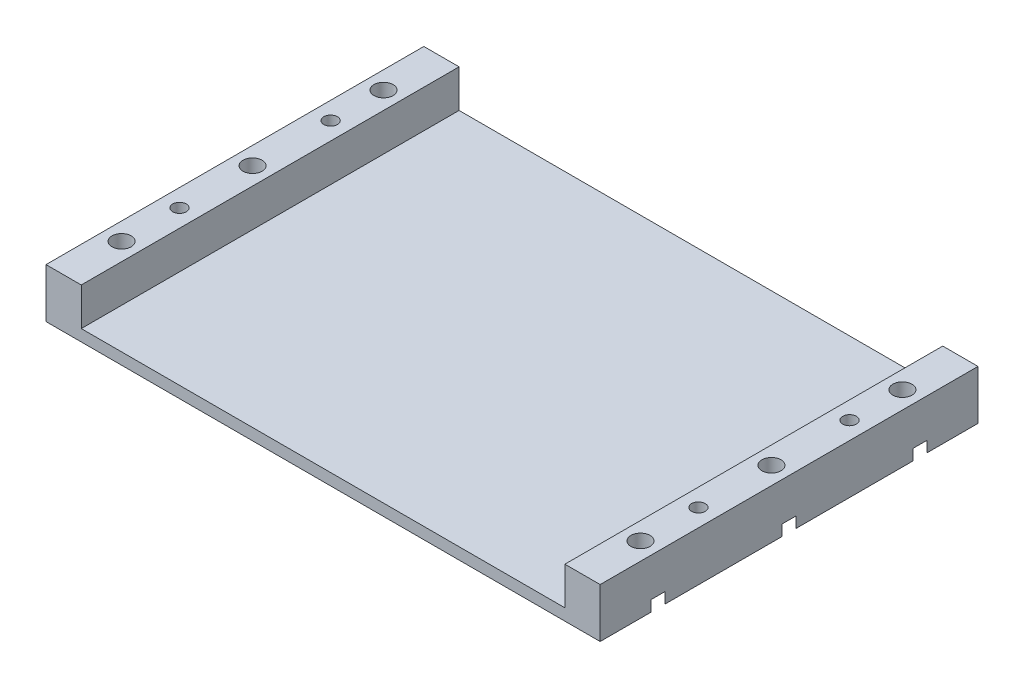
SolidWorks part; units mm, degrees
ref_plane "Front Plane" through (0, 0, 0) normal (0, 0, 1) x (1, 0, 0)
ref_plane "Top Plane" through (0, 0, 0) normal (0, 1, 0) x (1, 0, 0)
ref_plane "Right Plane" through (0, 0, 0) normal (1, 0, 0) x (0, 0, -1)
sketch "Sketch1" plane through (0, 0, 0) normal (0, 1, 0) x (1, 0, 0)
  line L0 (0, 73.5868) -> (1.4132, 75) construction
  line L1 (0, 0) -> (96, 0)
  line L2 (0, 0) -> (0, 75)
  line L3 (0, 75) -> (96, 75)
  line L4 (96, 0) -> (96, 75)
  line L5 (1.4132, 75) -> (94.5868, 75)
  line L6 (94.5868, 75) -> (96, 73.5868) construction
  line L7 (96, 73.5868) -> (96, 1.4132)
  line L8 (96, 1.4132) -> (94.5868, 0) construction
  line L9 (94.5868, 0) -> (1.4132, 0)
  line L10 (1.4132, 0) -> (0, 1.4132) construction
  line L11 (0, 1.4132) -> (0, 73.5868)
  dimension "D1" = 96
  dimension "D2" = 75
extrude "Boss-Extrude1" add sketch "Sketch1" along normal blind 2.3 contours L1 L4 L3 L2 region at (48, 0, -37.5)
ref_plane "center-of-slot" [suppressed] through (0, 1.143, 0) normal (0, 1, 0) x (1, 0, 0)
sketch "Sketch2" plane through (0, 2.3, 0) normal (0, 1, 0) x (1, 0, 0)
  line L0 (0, 0) -> (96, 0) construction
  line L1 (0, 75) -> (-7, 75)
  line L2 (0, 75) -> (0, 0)
  line L3 (0, 0) -> (-7, 0)
  line L4 (-7, 75) -> (-7, 0)
  dimension "D1" = 7
extrude "Boss-Extrude2" add sketch "Sketch2" along normal blind 7.5 and the other way up to surface (2.3 mm away) other way up to face at (48, 0, -37.5)
sketch "Sketch3" plane through (0, 2.3, 0) normal (0, 1, 0) x (1, 0, 0)
  line L0 (0, 0) -> (96, 0) construction
  line L1 (96, 75) -> (103, 75)
  line L2 (96, 75) -> (96, 0)
  line L3 (96, 0) -> (103, 0)
  line L4 (103, 75) -> (103, 0)
  line L5 (0, 75) -> (-7, 75) construction
extrude "Boss-Extrude3" add sketch "Sketch3" along normal up to surface and the other way up to surface up to face at (-3.5, 9.8, -37.5) other way up to face at (44.5, 0, -37.5)
hole_wizard "#6-32 Tapped Hole1" positions "Sketch5" profile "Sketch4" tap size "#6-32" standard "ANSI Inch" end condition through all
sketch "Sketch5" plane through (0, 0, 0) normal (0, -1, 0) x (-1, 0, 0)
  line L0 (-103, 75) -> (-103, 0) construction
  line L2 (7, 0) -> (-103, 0) construction
  line L3 (7, 75) -> (-103, 75) construction
  line L4 (7, 0) -> (7, 75) construction
  point P11 (-99.5, 23)
  point P13 (-99.5, 53)
  point P30 (3.5, 23)
  point P32 (3.5, 53)
  dimension "D1" = 3.5
  dimension "D2" = 23
  dimension "D3" = 22
  dimension "D4" = 3.5
sketch "Sketch4" plane through (99.5, 0, -23) normal (1, 0, 0) x (0, 0, -1)
  line L0 (0, 0) -> (0, 9.8)
  line L1 (0, 9.8) -> (1.3525, 9.8)
  line L3 (1.3525, 9.8) -> (1.3525, 7.01)
  line L4 (1.3525, 7.01) -> (1.7526, 7.01)
  line L5 (1.7526, 7.01) -> (1.7526, 0)
  line L7 (1.7526, 0) -> (0, 0)
  line L11 (0, -6.35) -> (0, 107.95) construction
  dimension "Thru Tap Drill Dia." = 2.7051
  dimension "Thru Tap Drill Depth" = 9.8
  dimension "Thread Major Dia." = 3.5052
  dimension "Thread Depth" = 7.01
hole_wizard "CBORE for #6 Button Head Cap Screw1" positions "Sketch7" profile "Sketch6" counterbore size "#6" standard "ANSI Inch" end condition through all
sketch "Sketch7" plane through (0, 0, 0) normal (0, -1, 0) x (-1, 0, 0)
  line L0 (-99.5, 63.5) -> (-99.5, 37.5) construction
  line L1 (-99.5, 37.5) -> (-99.5, 11.5) construction
  line L2 (-99.5, 11.5) -> (3.5, 11.5) construction
  line L3 (3.5, 11.5) -> (3.5, 37.5) construction
  line L4 (3.5, 37.5) -> (3.5, 63.5) construction
  line L6 (-99.5, 37.5) -> (-103, 37.5) construction
  line L7 (-103, 75) -> (-103, 0) construction
  line L9 (-99.5, 11.5) -> (-99.5, 23) construction
  line L11 (3.5, 11.5) -> (3.5, 23) construction
  circle A3 centre (-99.5, 23) radius 1.7526 construction
  point P0 (-99.5, 63.5)
  point P2 (-99.5, 37.5)
  point P4 (-99.5, 11.5)
  point P6 (3.5, 11.5)
  point P8 (3.5, 37.5)
  point P10 (3.5, 63.5)
  dimension "D1" = 26
sketch "Sketch6" plane through (99.5, 0, -63.5) normal (1, 0, 0) x (0, 0, -1)
  line L0 (0, 0) -> (0, 9.8)
  line L1 (0, 9.8) -> (1.8986, 9.8)
  line L3 (1.8986, 9.8) -> (1.8986, 2.1542)
  line L4 (1.8986, 2.1542) -> (3.7706, 2.1542)
  line L5 (3.7706, 2.1542) -> (3.7706, 0)
  line L7 (3.7706, 0) -> (0, 0)
  line L11 (0, -6.35) -> (0, 107.95) construction
  dimension "Thru Hole Dia." = 3.7973
  dimension "Thru Hole Depth" = 9.8
  dimension "C'Bore Dia." = 7.5413
  dimension "C'Bore Depth" = 2.1542
